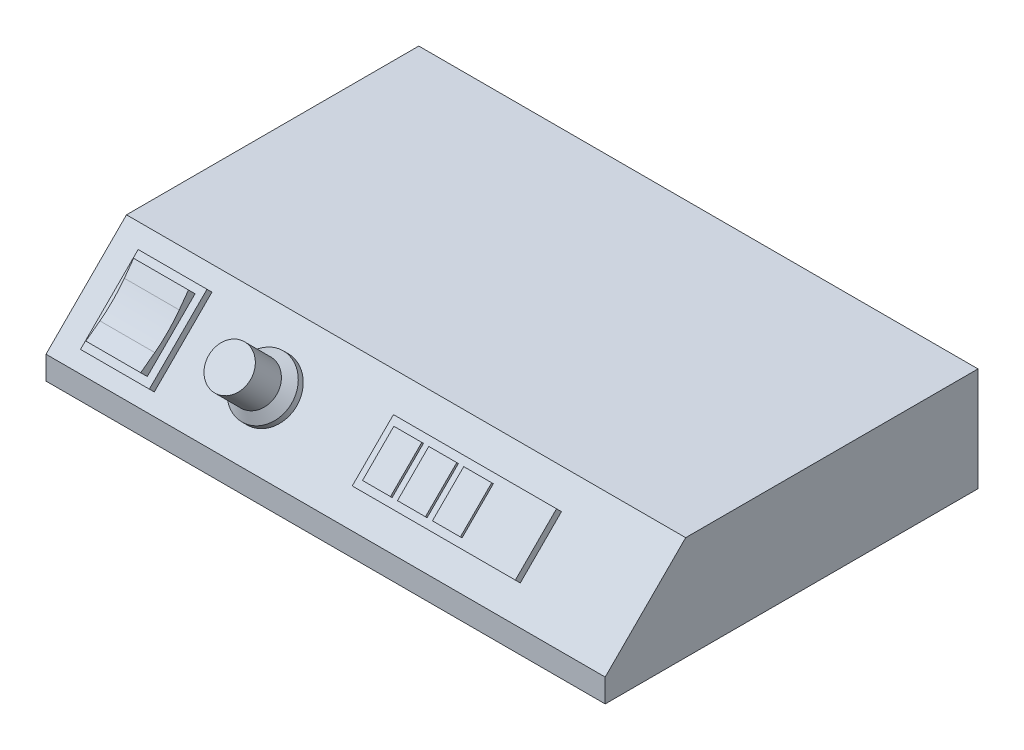
SolidWorks part; units mm, degrees
ref_plane "Front Plane" through (0, 0, 0) normal (0, 0, 1) x (1, 0, 0)
ref_plane "Top Plane" through (0, 0, 0) normal (0, 1, 0) x (1, 0, 0)
ref_plane "Right Plane" through (0, 0, 0) normal (1, 0, 0) x (0, 0, -1)
sketch "Sketch1" plane through (0, 0, 0) normal (1, 0, 0) x (0, 0, -1)
  line L0 (0, 0) -> (-66.7583, 0)
  line L1 (-66.7583, 0) -> (-66.7583, 10)
  line L2 (-66.7583, 10) -> (-32.2193, 44.5391)
  line L3 (-32.2193, 44.5391) -> (93.2417, 44.5391)
  line L4 (93.2417, 44.5391) -> (93.2417, 0)
  line L5 (93.2417, 0) -> (0, 0)
  dimension "D1" = 135
  dimension "D2" = 10
  dimension "D3" = 160
  dimension "D4" = 125.4609
extrude "Boss-Extrude1" add sketch "Sketch1" along normal blind 240
sketch "Sketch2" plane through (0, 38.3792, 38.3792) normal (0, 0.7071, 0.7071) x (1, 0, 0)
  line L0 (240, -40.1342) -> (0, -40.1342) construction
  line L1 (12.3304, 1.3658) -> (41.8765, 1.3658)
  line L2 (12.3304, 1.3658) -> (12.3304, -33.6342)
  line L3 (12.3304, -33.6342) -> (41.8765, -33.6342)
  line L4 (41.8765, 1.3658) -> (41.8765, -33.6342)
  line L5 (125.1818, -3.2886) -> (195.1818, -3.2886)
  line L6 (125.1818, -3.2886) -> (125.1818, -28.2886)
  line L7 (125.1818, -28.2886) -> (195.1818, -28.2886)
  line L8 (195.1818, -3.2886) -> (195.1818, -28.2886)
  line L11 (240, 8.7114) -> (0, 8.7114) construction
  circle A0 centre (77.8336, -15.7342) radius 12.5
  dimension "D2" = 25
  dimension "D1" = 35
  dimension "D3" = 25
  dimension "D4" = 70
  dimension "D5" = 6.5
  dimension "D6" = 24.4
  dimension "D7" = 12
extrude "Boss-Extrude2" add sketch "Sketch2" along normal blind 3 contours L8 L5 L6 L7 | L4 L1 L2 L3 | A0 region at (27.1035, 26.9706, 49.7878) region at (160.1818, 27.2149, 49.5434) region at (77.8336, 27.2534, 49.5049)
sketch "Sketch3" plane through (0, 40.5005, 40.5005) normal (0, 0.7071, 0.7071) x (1, 0, 0)
  circle A0 centre (77.8336, -15.7342) radius 9
  dimension "D1" = 18
extrude "Boss-Extrude3" add sketch "Sketch3" along normal blind 20
chamfer "Chamfer1" distance 3.5 angle 50 1 edges at (77.8336, 23.0108, 57.9902) first distance on face at (77.8336, 23.0108, 57.9902)
sketch "Sketch4" plane through (0, 40.5005, 40.5005) normal (0, 0.7071, 0.7071) x (1, 0, 0)
  line L0 (12.3304, 1.3658) -> (12.3304, -33.6342) construction
  line L1 (15.3304, -1.6342) -> (38.8765, -1.6342)
  line L2 (15.3304, -1.6342) -> (15.3304, -30.6342)
  line L3 (15.3304, -30.6342) -> (38.8765, -30.6342)
  line L4 (38.8765, -1.6342) -> (38.8765, -30.6342)
  line L5 (41.8765, 1.3658) -> (41.8765, -33.6342) construction
  line L6 (12.3304, 1.3658) -> (41.8765, 1.3658) construction
  line L7 (12.3304, -33.6342) -> (41.8765, -33.6342) construction
  dimension "D1" = 3
  dimension "D2" = 3
  dimension "D3" = 3
  dimension "D4" = 3
extrude "Boss-Extrude4" add sketch "Sketch4" along normal blind 4
sketch "Sketch5" plane through (15.3304, 0, 0) normal (-1, 0, 0) x (0, 0, 1)
  line L0 (54.5757, 32.3242) -> (51.6262, 29.3747) construction
  line L1 (60.9396, 25.9602) -> (48.2117, 38.6881) construction
  line L2 (41.656, 39.3449) -> (62.1621, 18.8388) construction
  line L3 (44.4845, 42.1734) -> (48.4552, 36.7455)
  line L4 (58.9606, 26.1543) -> (64.9906, 21.6673)
  line L5 (64.9906, 21.6673) -> (44.4845, 42.1734)
  arc A0 (48.4552, 36.7455) -> (58.9606, 26.1543) centre (88.8096, 66.2671) ccw
  point P9 (52.909, 30.6575)
  point P14 (52.909, 30.6575)
  dimension "D1" = 50
extrude "Cut-Extrude1" cut sketch "Sketch5" against normal blind 27
sketch "Sketch6" plane through (0, 40.5005, 40.5005) normal (0, 0.7071, 0.7071) x (1, 0, 0)
  line L0 (125.1818, -3.2886) -> (125.1818, -28.2886) construction
  line L1 (128.1818, -6.2886) -> (140.1818, -6.2886)
  line L2 (128.1818, -6.2886) -> (128.1818, -25.2886)
  line L3 (128.1818, -25.2886) -> (140.1818, -25.2886)
  line L4 (140.1818, -6.2886) -> (140.1818, -25.2886)
  line L5 (143.1818, -6.2886) -> (155.1818, -6.2886)
  line L6 (143.1818, -6.2886) -> (143.1818, -25.2886)
  line L7 (143.1818, -25.2886) -> (155.1818, -25.2886)
  line L8 (155.1818, -6.2886) -> (155.1818, -25.2886)
  line L9 (158.1818, -6.2886) -> (170.1818, -6.2886)
  line L10 (158.1818, -6.2886) -> (158.1818, -25.2886)
  line L11 (158.1818, -25.2886) -> (170.1818, -25.2886)
  line L12 (170.1818, -6.2886) -> (170.1818, -25.2886)
  line L13 (125.1818, -28.2886) -> (195.1818, -28.2886) construction
  line L14 (125.1818, -3.2886) -> (195.1818, -3.2886) construction
  line L15 (125.1818, -3.2886) -> (195.1818, -3.2886) construction
  point P20 (170.1818, -25.2886)
  point P21 (0, 0)
  dimension "D1" = 3
  dimension "D2" = 3
  dimension "D3" = 3
  dimension "D4" = 12
  dimension "D5" = 12
  dimension "D6" = 12
  dimension "D7" = 3
  dimension "D8" = 3
  dimension "D9" = 3
  dimension "D10" = 3
  dimension "D11" = 3
  dimension "D12" = 3
extrude "Boss-Extrude5" add sketch "Sketch6" along normal blind 1
